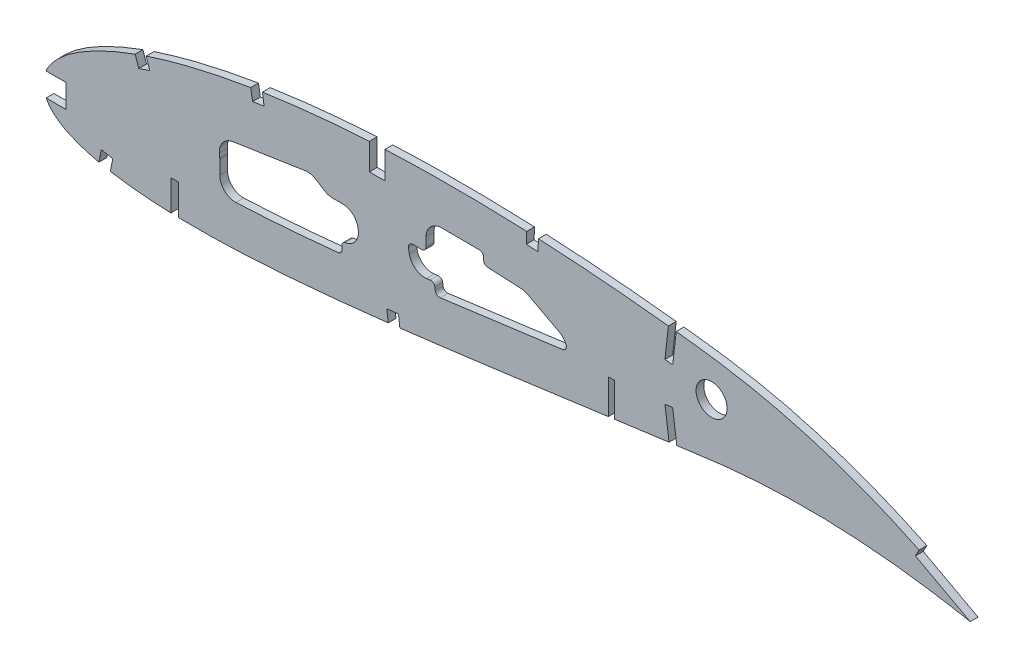
SolidWorks part; units mm, degrees
material "Plywood"
ref_plane "Front Plane" through (0, 0, 0) normal (0, 0, 1) x (1, 0, 0)
ref_plane "Top Plane" through (0, 0, 0) normal (0, 1, 0) x (1, 0, 0)
ref_plane "Right Plane" through (0, 0, 0) normal (1, 0, 0) x (0, 0, -1)
curve "Curve1"
  spline degree 3 poles (383.949, 0.5986, 0) (383.9196, 0.6168, 0) (383.802, 0.6894, 0) (383.5372, 0.8518, 0) (383.0962, 1.1224, 0) (382.4788, 1.4992, 0) (381.6856, 1.9812, 0) (380.716, 2.5651, 0) (379.5708, 3.249, 0) (378.2502, 4.0295, 0) (376.7543, 4.9032, 0) (375.0838, 5.8664, 0) (373.2387, 6.9137, 0) (371.2197, 8.0407, 0) (369.0276, 9.2423, 0) (366.6628, 10.5128, 0) (364.1261, 11.8459, 0) (361.4185, 13.2358, 0) (358.5405, 14.6749, 0) (355.4934, 16.1571, 0) (352.2782, 17.675, 0) (348.8962, 19.2207, 0) (345.3491, 20.7877, 0) (341.638, 22.3663, 0) (337.765, 23.9497, 0) (333.7318, 25.5289, 0) (329.5407, 27.0966, 0) (325.1933, 28.6428, 0) (320.6929, 30.1607, 0) (316.0417, 31.6403, 0) (311.2431, 33.0737, 0) (306.2997, 34.4516, 0) (301.2157, 35.767, 0) (295.9944, 37.0101, 0) (290.6401, 38.1728, 0) (285.1572, 39.2479, 0) (279.5502, 40.2249, 0) (273.8346, 41.1028, 0) (268.1025, 41.8331, 0) (262.3821, 42.5494, 0) (256.6703, 43.2222, 0) (250.8886, 43.8666, 0) (245.0428, 44.4788, 0) (239.1384, 45.057, 0) (233.1816, 45.5987, 0) (227.1785, 46.1022, 0) (221.135, 46.5647, 0) (215.0573, 46.9856, 0) (208.9515, 47.361, 0) (202.8242, 47.6908, 0) (196.6815, 47.9725, 0) (190.5298, 48.2044, 0) (184.3757, 48.385, 0) (178.2255, 48.5125, 0) (172.0859, 48.5861, 0) (165.9633, 48.6039, 0) (159.8643, 48.5655, 0) (153.7954, 48.4696, 0) (147.7632, 48.3149, 0) (141.7741, 48.1011, 0) (135.8345, 47.8283, 0) (129.951, 47.4942, 0) (124.1299, 47.1009, 0) (118.3778, 46.6469, 0) (112.701, 46.1319, 0) (107.1053, 45.5581, 0) (101.5971, 44.9239, 0) (96.1822, 44.2312, 0) (90.8666, 43.4813, 0) (85.6562, 42.6738, 0) (80.5566, 41.8111, 0) (75.5733, 40.894, 0) (70.7116, 39.9252, 0) (65.9768, 38.9049, 0) (61.3739, 37.8363, 0) (56.9076, 36.7211, 0) (52.5828, 35.5615, 0) (48.4038, 34.3602, 0) (44.375, 33.1199, 0) (40.5009, 31.842, 0) (36.7845, 30.5314, 0) (33.2304, 29.1889, 0) (29.8413, 27.8188, 0) (26.6212, 26.4228, 0) (23.5724, 25.0052, 0) (20.6984, 23.5677, 0) (18.0014, 22.1143, 0) (15.4839, 20.6472, 0) (13.1483, 19.1691, 0) (10.9958, 17.6837, 0) (9.0293, 16.1921, 0) (7.2493, 14.698, 0) (5.6571, 13.2036, 0) (4.255, 11.71, 0) (3.0428, 10.2198, 0) (2.0222, 8.7343, 0) (1.1933, 7.2547, 0) (0.558, 5.7822, 0) (0.1157, 4.3176, 0) (-0.1263, 2.863, 0) (-0.1866, 1.4174, 0) (-0.0621, 0.4718, 0) (0, 0, 0) knots 0 0 0 0 0.000254 0.001015 0.002283 0.004057 0.006331 0.009105 0.012374 0.016134 0.02038 0.025106 0.030306 0.035972 0.0421 0.048678 0.055702 0.06316 0.071046 0.07935 0.088063 0.097176 0.106678 0.116562 0.126814 0.137428 0.148394 0.1597 0.171338 0.183298 0.19557 0.208144 0.221012 0.234162 0.247587 0.261277 0.275223 0.289414 0.303771 0.317689 0.331784 0.34604 0.360444 0.374983 0.38964 0.404403 0.419257 0.434187 0.449177 0.464215 0.479284 0.49437 0.509458 0.524532 0.539579 0.554583 0.56953 0.584403 0.599191 0.613877 0.628447 0.642889 0.657186 0.671326 0.685294 0.699078 0.712665 0.726043 0.739198 0.752118 0.764792 0.777208 0.789356 0.801224 0.812804 0.824083 0.835055 0.84571 0.856038 0.866034 0.875689 0.884998 0.893953 0.902553 0.910789 0.918661 0.926166 0.933303 0.940071 0.946475 0.952518 0.958205 0.963547 0.968557 0.97325 0.977651 0.981787 0.985694 0.989415 0.993001 0.996508 1 1 1 1
curve "Curve2"
  spline degree 3 poles (0, 0, 0) (0.0986, -0.4654, 0) (0.2962, -1.3985, 0) (0.8332, -2.7416, 0) (1.5434, -4.0328, 0) (2.4415, -5.2686, 0) (3.5218, -6.4485, 0) (4.7818, -7.574, 0) (6.2202, -8.6443, 0) (7.8352, -9.659, 0) (9.6244, -10.6191, 0) (11.5859, -11.5241, 0) (13.7178, -12.3737, 0) (16.0178, -13.1667, 0) (18.4831, -13.9043, 0) (21.1113, -14.5848, 0) (23.8995, -15.2091, 0) (26.845, -15.7756, 0) (29.9446, -16.2848, 0) (33.195, -16.7366, 0) (36.593, -17.1311, 0) (40.1351, -17.4676, 0) (43.8179, -17.7467, 0) (47.6377, -17.9687, 0) (51.5909, -18.1343, 0) (55.6735, -18.2428, 0) (59.8817, -18.2959, 0) (64.2115, -18.2945, 0) (68.6589, -18.238, 0) (73.2199, -18.1297, 0) (77.8902, -17.9689, 0) (82.6657, -17.7575, 0) (87.5419, -17.4976, 0) (92.5144, -17.1902, 0) (97.5791, -16.8365, 0) (102.7313, -16.4394, 0) (107.9665, -16, 0) (113.2801, -15.5207, 0) (118.6674, -15.0039, 0) (124.1237, -14.4514, 0) (129.6442, -13.8657, 0) (135.2241, -13.2487, 0) (140.8584, -12.6036, 0) (146.5422, -11.9317, 0) (152.2705, -11.2369, 0) (158.0381, -10.5203, 0) (163.84, -9.7848, 0) (169.6711, -9.0339, 0) (175.5259, -8.2674, 0) (181.3995, -7.4908, 0) (187.2862, -6.7036, 0) (193.1809, -5.9096, 0) (199.0781, -5.1115, 0) (204.9721, -4.3094, 0) (210.8578, -3.5066, 0) (216.7295, -2.7054, 0) (222.5817, -1.9059, 0) (228.409, -1.112, 0) (234.2055, -0.3236, 0) (239.9659, 0.4577, 0) (245.6847, 1.2295, 0) (251.3565, 1.9909, 0) (256.9754, 2.7413, 0) (262.5357, 3.4812, 0) (267.9487, 4.188, 0) (273.2002, 4.8993, 0) (278.3079, 5.4825, 0) (283.3519, 5.9802, 0) (288.3377, 6.3883, 0) (293.259, 6.7125, 0) (298.1104, 6.9553, 0) (302.886, 7.1201, 0) (307.5799, 7.2116, 0) (312.186, 7.2323, 0) (316.6983, 7.1886, 0) (321.1107, 7.0842, 0) (325.4171, 6.9238, 0) (329.6115, 6.7126, 0) (333.688, 6.4566, 0) (337.6405, 6.1594, 0) (341.4634, 5.828, 0) (345.1508, 5.4673, 0) (348.6971, 5.0813, 0) (352.0971, 4.6782, 0) (355.3453, 4.2606, 0) (358.4369, 3.8354, 0) (361.3669, 3.4069, 0) (364.1307, 2.9806, 0) (366.7239, 2.5605, 0) (369.1422, 2.1521, 0) (371.3821, 1.7594, 0) (373.4394, 1.3862, 0) (375.3115, 1.0371, 0) (376.9946, 0.7139, 0) (378.4864, 0.4219, 0) (379.7842, 0.1625, 0) (380.886, -0.0608, 0) (381.79, -0.247, 0) (382.4947, -0.3932, 0) (382.9989, -0.4995, 0) (383.3019, -0.5627, 0) (383.4365, -0.5914, 0) (383.4701, -0.5986, 0) knots 0 0 0 0 0.003638 0.007293 0.011028 0.014901 0.018963 0.023258 0.027821 0.032679 0.037853 0.043362 0.049215 0.055422 0.061989 0.068918 0.076211 0.083868 0.091887 0.100266 0.109 0.118085 0.127515 0.137285 0.147388 0.157816 0.168563 0.179619 0.190977 0.202627 0.21456 0.226767 0.239236 0.251959 0.264924 0.27812 0.291536 0.30516 0.318981 0.332985 0.347163 0.361499 0.375981 0.390597 0.405333 0.420175 0.43511 0.450124 0.465203 0.480333 0.495501 0.51069 0.525887 0.541078 0.556247 0.571382 0.586466 0.601485 0.616424 0.631269 0.646007 0.660621 0.675098 0.689423 0.703582 0.716908 0.730009 0.742952 0.755726 0.76832 0.780724 0.792927 0.804916 0.816679 0.828204 0.839475 0.850481 0.861208 0.871639 0.881763 0.891564 0.901027 0.910139 0.918884 0.927249 0.935221 0.942785 0.949928 0.956638 0.962904 0.968712 0.974054 0.978918 0.983297 0.98718 0.990561 0.993433 0.995791 0.99763 0.998946 0.999737 1 1 1 1
sketch "Sketch1" plane through (0, 0, 0) normal (0, 0, 1) x (1, 0, 0)
  line L23 (383.4597, -0.5986) -> (387.1511, -1.386)
  line L24 (383.9386, 0.5986) -> (387.1511, -1.386)
  spline S4 degree 3 poles (0, 0) (0.0986, -0.4654) (0.2962, -1.3984) (0.8332, -2.7416) (1.5433, -4.0327) (2.4415, -5.2684) (3.5217, -6.4484) (4.7816, -7.5738) (6.22, -8.6441) (7.835, -9.6587) (9.6242, -10.6188) (11.5856, -11.5238) (13.7174, -12.3733) (16.0173, -13.1663) (18.4826, -13.9039) (21.1108, -14.5844) (23.8989, -15.2087) (26.8443, -15.7751) (29.9438, -16.2844) (33.1941, -16.7361) (36.592, -17.1306) (40.134, -17.4671) (43.8167, -17.7462) (47.6365, -17.9682) (51.5895, -18.1338) (55.672, -18.2423) (59.88, -18.2954) (64.2098, -18.294) (68.657, -18.2375) (73.2179, -18.1293) (77.8881, -17.9684) (82.6634, -17.757) (87.5395, -17.4972) (92.5119, -17.1897) (97.5764, -16.836) (102.7286, -16.439) (107.9636, -15.9995) (113.2771, -15.5202) (118.6642, -15.0035) (124.1204, -14.451) (129.6407, -13.8653) (135.2204, -13.2483) (140.8546, -12.6033) (146.5382, -11.9314) (152.2664, -11.2365) (158.0338, -10.52) (163.8356, -9.7845) (169.6665, -9.0336) (175.5212, -8.2672) (181.3946, -7.4906) (187.2811, -6.7034) (193.1757, -5.9095) (199.0727, -5.1113) (204.9666, -4.3092) (210.8521, -3.5065) (216.7237, -2.7054) (222.5757, -1.9059) (228.4028, -1.112) (234.1992, -0.3236) (239.9594, 0.4576) (245.6781, 1.2294) (251.3497, 1.9908) (256.9684, 2.7413) (262.5286, 3.4811) (267.9415, 4.1879) (273.1928, 4.8992) (278.3003, 5.4823) (283.3443, 5.98) (288.3299, 6.3881) (293.2511, 6.7123) (298.1023, 6.9552) (302.8778, 7.1199) (307.5715, 7.2114) (312.1776, 7.2321) (316.6897, 7.1884) (321.102, 7.084) (325.4083, 6.9236) (329.6026, 6.7124) (333.679, 6.4564) (337.6313, 6.1592) (341.4541, 5.8278) (345.1414, 5.4671) (348.6876, 5.0812) (352.0875, 4.6781) (355.3357, 4.2605) (358.4272, 3.8353) (361.3571, 3.4068) (364.1208, 2.9805) (366.7139, 2.5604) (369.1322, 2.1521) (371.372, 1.7594) (373.4293, 1.3862) (375.3013, 1.0371) (376.9844, 0.7139) (378.4761, 0.4219) (379.7739, 0.1625) (380.8757, -0.0608) (381.7796, -0.247) (382.4844, -0.3932) (382.9885, -0.4994) (383.2915, -0.5627) (383.4261, -0.5914) (383.4597, -0.5986) knots 0 0 0 0 0.003638 0.007293 0.011028 0.014901 0.018963 0.023258 0.027821 0.032679 0.037853 0.043362 0.049215 0.055422 0.061989 0.068918 0.076211 0.083868 0.091887 0.100266 0.109 0.118085 0.127515 0.137285 0.147388 0.157816 0.168563 0.179619 0.190977 0.202627 0.21456 0.226767 0.239236 0.251959 0.264924 0.27812 0.291536 0.30516 0.318981 0.332985 0.347163 0.361499 0.375981 0.390597 0.405333 0.420175 0.43511 0.450124 0.465203 0.480333 0.495501 0.51069 0.525887 0.541078 0.556247 0.571382 0.586466 0.601485 0.616424 0.631269 0.646007 0.660621 0.675098 0.689423 0.703582 0.716908 0.730009 0.742952 0.755726 0.76832 0.780724 0.792927 0.804916 0.816679 0.828204 0.839475 0.850481 0.861208 0.871639 0.881763 0.891564 0.901027 0.910139 0.918884 0.927249 0.935221 0.942785 0.949928 0.956638 0.962904 0.968712 0.974054 0.978918 0.983297 0.98718 0.990561 0.993433 0.995791 0.99763 0.998946 0.999737 1 1 1 1
  spline S5 degree 3 poles (383.9386, 0.5986) (383.9092, 0.6167) (383.7916, 0.6893) (383.5268, 0.8518) (383.0858, 1.1223) (382.4685, 1.4991) (381.6752, 1.9811) (380.7057, 2.565) (379.5606, 3.2489) (378.24, 4.0294) (376.7441, 4.9031) (375.0736, 5.8662) (373.2286, 6.9135) (371.2097, 8.0405) (369.0176, 9.242) (366.6529, 10.5125) (364.1162, 11.8456) (361.4087, 13.2354) (358.5307, 14.6745) (355.4837, 16.1566) (352.2687, 17.6745) (348.8867, 19.2201) (345.3398, 20.7871) (341.6288, 22.3657) (337.7559, 23.949) (333.7228, 25.5282) (329.5317, 27.0959) (325.1845, 28.642) (320.6843, 30.1598) (316.0332, 31.6395) (311.2346, 33.0728) (306.2914, 34.4507) (301.2076, 35.766) (295.9864, 37.0091) (290.6322, 38.1717) (285.1495, 39.2469) (279.5426, 40.2238) (273.8272, 41.1017) (268.0952, 41.832) (262.375, 42.5482) (256.6633, 43.2211) (250.8818, 43.8654) (245.0361, 44.4776) (239.1319, 45.0558) (233.1753, 45.5974) (227.1724, 46.1009) (221.129, 46.5635) (215.0515, 46.9843) (208.9459, 47.3597) (202.8187, 47.6895) (196.6762, 47.9712) (190.5246, 48.2031) (184.3707, 48.3836) (178.2206, 48.5111) (172.0812, 48.5848) (165.9588, 48.6026) (159.86, 48.5642) (153.7912, 48.4683) (147.7592, 48.3136) (141.7702, 48.0998) (135.8308, 47.827) (129.9475, 47.4929) (124.1266, 47.0997) (118.3746, 46.6456) (112.6979, 46.1306) (107.1024, 45.5568) (101.5944, 44.9227) (96.1796, 44.23) (90.8641, 43.4801) (85.6539, 42.6727) (80.5544, 41.81) (75.5713, 40.8929) (70.7097, 39.9241) (65.975, 38.9039) (61.3722, 37.8353) (56.906, 36.7201) (52.5814, 35.5606) (48.4025, 34.3593) (44.3738, 33.119) (40.4998, 31.8412) (36.7835, 30.5306) (33.2295, 29.1881) (29.8405, 27.818) (26.6204, 26.4221) (23.5718, 25.0045) (20.6979, 23.5671) (18.0009, 22.1137) (15.4834, 20.6466) (13.148, 19.1685) (10.9955, 17.6833) (9.029, 16.1917) (7.2491, 14.6976) (5.657, 13.2033) (4.2548, 11.7097) (3.0427, 10.2196) (2.0221, 8.734) (1.1932, 7.2545) (0.558, 5.782) (0.1157, 4.3174) (-0.1263, 2.8629) (-0.1866, 1.4173) (-0.0621, 0.4717) (0, 0) knots 0 0 0 0 0.000254 0.001015 0.002283 0.004057 0.006331 0.009105 0.012374 0.016134 0.02038 0.025106 0.030306 0.035972 0.0421 0.048678 0.055702 0.06316 0.071046 0.07935 0.088063 0.097176 0.106678 0.116562 0.126814 0.137428 0.148394 0.1597 0.171338 0.183298 0.19557 0.208144 0.221012 0.234162 0.247587 0.261277 0.275223 0.289414 0.303771 0.317689 0.331784 0.34604 0.360444 0.374983 0.38964 0.404403 0.419257 0.434187 0.449177 0.464215 0.479284 0.49437 0.509458 0.524532 0.539579 0.554583 0.56953 0.584403 0.599191 0.613877 0.628447 0.642889 0.657186 0.671326 0.685294 0.699078 0.712665 0.726043 0.739198 0.752118 0.764792 0.777208 0.789356 0.801224 0.812804 0.824083 0.835055 0.84571 0.856038 0.866034 0.875689 0.884998 0.893953 0.902553 0.910789 0.918661 0.926166 0.933303 0.940071 0.946475 0.952518 0.958205 0.963547 0.968557 0.97325 0.977651 0.981787 0.985694 0.989415 0.993001 0.996508 1 1 1 1
extrude "Boss-Extrude1" add sketch "Sketch1" along normal blind 3.175
sketch "Sketch2" plane through (0, 0, 0) normal (0, 0, -1) x (-1, 0, 0)
  line L0 (-232.8305, 13.2238) -> (-230.2905, 13.2238)
  line L1 (-232.8305, -0.5032) -> (-232.8305, -2.8497)
  line L2 (-232.8305, 13.2238) -> (-232.8305, -0.5032)
  line L4 (-232.8305, -2.8497) -> (-230.2905, -1.6764)
  line L5 (-230.2905, -1.6764) -> (-230.2905, -0.5032)
  line L7 (-139.168, 47.9082) -> (-139.168, 36.8678)
  line L8 (-139.168, 36.8678) -> (-132.818, 36.8678)
  line L9 (-139.168, 47.9082) -> (-139.168, 49.4489)
  line L10 (-55.0305, -5.6829) -> (-55.0305, -17.799)
  line L12 (-139.168, 49.4489) -> (-132.818, 49.1679)
  line L13 (-132.818, 49.1679) -> (-132.818, 47.9082)
  line L14 (-51.8555, -5.6829) -> (-51.8555, -17.799)
  line L16 (-55.0305, -5.6829) -> (-51.8555, -5.6829)
  line L17 (-55.0305, -17.799) -> (-55.0305, -19.968)
  line L19 (-132.818, 47.9082) -> (-132.818, 36.8678)
  line L20 (-55.0305, -19.968) -> (-51.8555, -18.5014)
  line L21 (-51.8555, -18.5014) -> (-51.8555, -17.799)
  line L22 (-230.2905, 13.2238) -> (-230.2905, -0.5032)
extrude "Cut-Extrude1" cut sketch "Sketch2" against normal blind 7.62
sketch "Sketch3" plane through (0, 0, 0) normal (0, 0, -1) x (-1, 0, 0)
  circle A1 centre (-272.4199, 26.2554) radius 6.35
extrude "Cut-Extrude2" cut sketch "Sketch3" against normal blind 7.62
sketch "Sketch4" plane through (0, 0, 3.175) normal (0, 0, 1) x (1, 0, 0)
  line L0 (253.3978, 15.0563) -> (255.0785, 2.468)
  line L1 (253.3978, 15.0563) -> (255.0785, 2.468)
  line L2 (256.5449, 15.4765) -> (253.3978, 15.0563)
  line L3 (256.5449, 15.4765) -> (253.3978, 15.0563)
  line L4 (254.8081, 43.5209) -> (253.3898, 30.9004)
  line L5 (254.8081, 43.5209) -> (253.3898, 30.9004)
  line L6 (197.0245, 48.0319) -> (196.82, 43.2872)
  line L7 (197.0245, 48.0319) -> (196.82, 43.2872)
  line L8 (84.4023, 42.5499) -> (85.1717, 37.8779)
  line L9 (84.4023, 42.5499) -> (85.1717, 37.8779)
  line L10 (139.9591, -7.9331) -> (140.5078, -12.6647)
  line L11 (139.9591, -7.9331) -> (140.5078, -12.6647)
  line L12 (144.6885, -7.3719) -> (139.9591, -7.9331)
  line L13 (144.6885, -7.3719) -> (139.9591, -7.9331)
  line L14 (37.2314, 30.8049) -> (38.732, 26.3414)
  line L15 (37.2314, 30.8049) -> (38.732, 26.3414)
  line L16 (23.4683, -9.9368) -> (22.5446, -14.6116)
  line L17 (23.4683, -9.9368) -> (22.5446, -14.6116)
  line L18 (28.1358, -10.8598) -> (23.4683, -9.9368)
  line L19 (28.1358, -10.8598) -> (23.4683, -9.9368)
  line L20 (-0.4208, 6.5685) -> (9.1042, 6.5685)
  line L21 (-0.4208, 6.5685) -> (9.1042, 6.5685)
  line L22 (9.1042, -2.9565) -> (9.1042, 6.5685)
  line L23 (9.1042, -2.9565) -> (9.1042, 6.5685)
  line L24 (-0.4208, -2.9565) -> (9.1042, -2.9565)
  line L25 (-0.4208, -2.9565) -> (9.1042, -2.9565)
  line L26 (27.1866, -15.6474) -> (28.1358, -10.8598)
  line L27 (27.1866, -15.6474) -> (28.1358, -10.8598)
  line L28 (43.2462, 27.8589) -> (41.731, 32.3666)
  line L29 (43.2462, 27.8589) -> (41.731, 32.3666)
  line L30 (38.732, 26.3414) -> (43.2462, 27.8589)
  line L31 (38.732, 26.3414) -> (43.2462, 27.8589)
  line L32 (89.8796, 38.5972) -> (89.1598, 43.3084)
  line L33 (89.8796, 38.5972) -> (89.1598, 43.3084)
  line L34 (85.1717, 37.8779) -> (89.8796, 38.5972)
  line L35 (85.1717, 37.8779) -> (89.8796, 38.5972)
  line L36 (145.2504, -12.1074) -> (144.6885, -7.3719)
  line L37 (145.2504, -12.1074) -> (144.6885, -7.3719)
  line L38 (201.5767, 43.0552) -> (201.8123, 47.81)
  line L39 (201.5767, 43.0552) -> (201.8123, 47.81)
  line L40 (196.82, 43.2872) -> (201.5767, 43.0552)
  line L41 (196.82, 43.2872) -> (201.5767, 43.0552)
  line L42 (258.2214, 2.8872) -> (256.5449, 15.4765)
  line L43 (258.2214, 2.8872) -> (256.5449, 15.4765)
  line L44 (256.5449, 30.5458) -> (258.0069, 43.1557)
  line L45 (256.5449, 30.5458) -> (258.0069, 43.1557)
  line L46 (253.3898, 30.9004) -> (256.5449, 30.5458)
  line L47 (253.3898, 30.9004) -> (256.5449, 30.5458)
  line L48 (-0.4208, -2.9565) -> (-0.4208, 6.5685)
  line L49 (22.5446, -14.6116) -> (21.6044, -19.3694)
  line L50 (21.6044, -19.3694) -> (26.2707, -20.2914)
  line L51 (26.2707, -20.2914) -> (27.1866, -15.6474)
  line L52 (84.4023, 42.5499) -> (89.1598, 43.3084)
  line L53 (140.5078, -12.6647) -> (145.2504, -12.1074)
  line L54 (197.0245, 48.0319) -> (201.8123, 47.81)
  line L55 (254.8081, 43.5209) -> (258.0069, 43.1557)
  line L56 (255.0785, 2.468) -> (255.3213, 0.6492)
  line L57 (255.3213, 0.6492) -> (258.4684, 1.0693)
  line L58 (258.4684, 1.0693) -> (258.2214, 2.8872)
  spline S0 degree 3 poles (-926.9744, 1759.2326) (537.7565, -123.458) (52.1572, 240.1265) (-170.353, -168.2622) (607.2071, -1871.7177) knots -132.16721 -132.16721 -132.16721 -132.16721 0.273428 83.465389 83.465389 83.465389 83.465389 only from (41.731, 32.3666) to (37.2314, 30.8049)
  spline S1 degree 3 poles (41.731, 32.3666) (41.3193, 32.2289) (39.8151, 31.7207) (38.3166, 31.1959) (37.2314, 30.8049) knots 0 0 0 0 0.273428 1 1 1 1
extrude "Cut-Extrude3" cut sketch "Sketch4" against normal through all
sketch "Sketch5" plane through (0, 0, 3.175) normal (0, 0, 1) x (1, 0, 0)
  line L0 (127.2472, 20.1038) -> (116.054, 20.1038)
  line L3 (108.9829, 24.5572) -> (71.3232, 18.8038)
  line L9 (71.7945, 11.0811) -> (71.7945, -1.3909)
  line L10 (121.9103, 2.1782) -> (121.3808, 6.7439)
  line L11 (121.3808, 6.7439) -> (129.4239, 7.6984)
  line L12 (127.2472, 20.1038) -> (129.4239, 7.6984)
  line L13 (125.7357, 28.718) -> (131.3266, -3.1455) construction
  line L14 (79.1937, 35.0998) -> (49.8476, 28.1498) construction
  line L15 (121.3808, 6.7439) -> (149.0188, 10.0236) construction
  line L16 (145.518, 20.1038) -> (116.054, 20.1038) construction
  line L17 (70.732, 22.3937) -> (63.3562, 20.647) construction
  line L18 (71.3232, 18.8038) -> (71.7945, 11.0811)
  line L19 (116.054, 20.1038) -> (108.9829, 24.5572)
  line L20 (126.468, 40.8897) -> (96.4185, 37.8427) construction
  line L21 (116.054, 29.3663) -> (108.3673, 28.5869) construction
  line L22 (150.1388, 10.1565) -> (159.3602, 11.2507)
  line L23 (159.3602, 11.2507) -> (159.9102, 6.616)
  line L24 (213.5265, 13.7782) -> (213.5265, 17.324)
  line L25 (213.5265, 17.324) -> (213.5265, 17.324)
  line L26 (213.5265, 17.324) -> (196.0856, 26.5391)
  line L27 (196.0856, 26.5391) -> (179.3537, 27.3552)
  line L28 (179.3537, 27.3552) -> (179.5415, 31.7126)
  line L29 (155.932, 31.7324) -> (155.932, 20.1038)
  line L30 (131.6947, 7.9678) -> (159.3602, 11.2507) construction
  line L31 (148.3934, 20.1038) -> (150.1388, 10.1565)
  line L32 (146.2503, 32.3176) -> (151.8412, 0.454) construction
  line L33 (155.932, 20.1038) -> (148.3934, 20.1038)
  line L36 (43.0125, 21.0812) -> (53.443, 0.6671) construction
  line L37 (135.993, 30.5178) -> (141.5839, -1.3457) construction
  line L38 (231.5605, 19.5738) -> (198.9045, 36.828) construction
  line L110 (53.443, 0.6671) -> (61.3805, 0.6671) construction
  line L111 (61.3805, 0.6671) -> (61.3805, -11.942) construction
  line L112 (133.4644, -7.0518) -> (132.9219, -2.3736) construction
  line L113 (132.9219, -2.3736) -> (150.2459, -0.3179) construction
  line L114 (150.2459, -0.3179) -> (150.8034, -5.0156) construction
  line L115 (223.9405, 4.6886) -> (223.9405, 19.5738) construction
  line L116 (223.9405, 19.5738) -> (231.5605, 19.5738) construction
  line L125 (198.9045, 36.828) -> (190.204, 37.2524) construction
  line L126 (190.204, 37.2524) -> (190.4019, 41.8451) construction
  line L127 (145.518, 41.8768) -> (145.518, 30.5178) construction
  line L128 (145.518, 30.5178) -> (126.468, 30.5178) construction
  line L129 (126.468, 30.5178) -> (126.468, 40.8897) construction
  line L130 (96.4185, 37.8427) -> (97.1157, 33.279) construction
  line L131 (97.1157, 33.279) -> (79.9261, 30.6529) construction
  line L132 (79.9261, 30.6529) -> (79.1937, 35.0998) construction
  line L133 (49.8476, 28.1498) -> (51.2885, 23.8632) construction
  line L134 (51.2885, 23.8632) -> (43.0125, 21.0812) construction
  line L135 (59.8167, 11.0811) -> (71.7945, 11.0811) construction
  line L136 (57.7836, 15.06) -> (59.8167, 11.0811) construction
  line L137 (64.4778, 17.3103) -> (57.7836, 15.06) construction
  line L138 (63.3562, 20.647) -> (64.4778, 17.3103) construction
  line L139 (71.3232, 18.8038) -> (70.732, 22.3937) construction
  line L140 (116.054, 20.1038) -> (116.054, 29.3663) construction
  line L141 (108.3673, 28.5869) -> (108.9829, 24.5572) construction
  line L142 (155.932, 20.1038) -> (126.468, 20.1038) construction
  spline S0 degree 1 poles (159.9102, 6.616) (213.5265, 13.7782) knots 0 0 1 1 construction
  spline S1 degree 1 poles (179.5415, 31.7126) (155.932, 31.7324) knots 0 0 1 1 construction
  spline S2 degree 1 poles (71.7945, -1.3909) (121.9103, 2.1782) knots 0 0 1 1 construction
  spline S3 degree 3 poles (159.9102, 6.616) (164.3746, 7.1833) (173.2961, 8.3408) (186.698, 10.1292) (200.1064, 11.946) (209.054, 13.1676) (213.5265, 13.7782) knots 0.142323 0.142323 0.142323 0.142323 0.325945 0.509567 0.693189 0.876811 0.876811 0.876811 0.876811
  spline S4 degree 3 poles (179.5415, 31.7126) (177.5729, 31.7494) (173.6348, 31.8061) (167.7311, 31.8388) (161.8287, 31.8179) (157.8978, 31.7672) (155.932, 31.7324) knots 0.237664 0.237664 0.237664 0.237664 0.371263 0.504863 0.638463 0.772063 0.772063 0.772063 0.772063
  spline S5 degree 3 poles (71.7945, -1.3909) (75.9548, -1.2787) (84.2564, -0.9305) (96.788, -0.1167) (109.3347, 0.9275) (117.723, 1.7458) (121.9103, 2.1782) knots 0.147972 0.147972 0.147972 0.147972 0.32451 0.501048 0.677586 0.854123 0.854123 0.854123 0.854123
  spline S36 degree 3 poles (61.3805, -11.942) (67.4058, -11.9519) (73.4269, -11.8005) (85.4632, -11.2817) (91.4772, -10.9139) (103.4919, -10.0249) (109.4942, -9.5033) (121.4867, -8.3518) (127.4774, -7.7211) (133.4644, -7.0518) knots 0 0 0 0 0.25 0.25 0.5 0.5 0.75 0.75 1 1 1 1 construction
  spline S37 degree 3 poles (150.8034, -5.0156) (163.0088, -3.5214) (175.2005, -1.9186) (199.5744, 1.3563) (211.7567, 3.028) (223.9405, 4.6886) knots 0 0 0 0 0.5 0.5 1 1 1 1 construction
  spline S41 degree 3 poles (190.4019, 41.8451) (182.9238, 42.0966) (175.442, 42.2337) (160.4781, 42.2535) (152.996, 42.1371) (145.518, 41.8768) knots 0 0 0 0 0.5 0.5 1 1 1 1 construction
  spline S42 degree 3 poles (126.468, 40.8897) (116.4216, 40.191) (106.3976, 39.1999) (96.4185, 37.8427) knots 0 0 0 0 1 1 1 1 construction
  spline S43 degree 3 poles (79.1937, 35.0998) (74.2467, 34.1892) (69.3194, 33.1701) (59.5289, 30.8714) (54.667, 29.5931) (49.8476, 28.1498) knots 0 0 0 0 0.5 0.5 1 1 1 1 construction
  dimension "D1" = 10.414
  dimension "D2" = 10.414
  dimension "D3" = 10.414
extrude "Cut-Extrude4" cut sketch "Sketch5" against normal blind 7.62
fillet "Fillet1" radius 6.35 11 edges at (150.1388, 10.1565, 1.5875) (213.5265, 17.324, 1.5875) (155.932, 31.7324, 1.5875) (196.0856, 26.5391, 1.5875) (129.4239, 7.6984, 1.5875) (127.2472, 20.1038, 1.5875) (116.054, 20.1038, 1.5875) (108.9829, 24.5572, 1.5875) (71.7945, -1.3909, 1.5875) (71.7945, 11.0811, 1.5875) (71.3232, 18.8038, 1.5875)
fillet "Fillet2" radius 1.778 9 edges at (213.5265, 13.7782, 1.5875) (179.3537, 27.3552, 1.5875) (179.5415, 31.7126, 1.5875) (159.9102, 6.616, 1.5875) (159.3602, 11.2507, 1.5875) (155.932, 20.1038, 1.5875) (148.3934, 20.1038, 1.5875) (121.9103, 2.1782, 1.5875) (121.3808, 6.7439, 1.5875)
sketch "Sketch6" plane through (0, 0, 3.175) normal (0, 0, 1) x (1, 0, 0)
  line L0 (357.0755, 15.3806) -> (355.5684, 12.586)
  line L1 (357.0755, 15.3806) -> (379.4317, 3.3241)
  line L2 (355.5684, 12.586) -> (377.9247, 0.5296)
  line L3 (379.4317, 3.3241) -> (377.9247, 0.5296)
  line L4 (383.4597, -0.5986) -> (387.1511, -1.386) construction
  line L5 (387.1511, -1.386) -> (383.9386, 0.5986) construction
  line L6 (383.4597, -0.5986) -> (387.1511, -1.386)
  line L7 (387.1511, -1.386) -> (383.9386, 0.5986)
  spline S0 degree 3 poles (-542.4415, 1804.8935) (-113.3574, -70.3051) (74.8659, -21.0222) (267.9415, 4.1879) (273.1928, 4.8992) (278.3003, 5.4823) (283.3443, 5.98) (288.3299, 6.3881) (293.2511, 6.7123) (298.1023, 6.9552) (302.8778, 7.1199) (307.5715, 7.2114) (312.1776, 7.2321) (316.6897, 7.1884) (321.102, 7.084) (325.4083, 6.9236) (329.6026, 6.7124) (333.679, 6.4564) (337.6313, 6.1592) (341.4541, 5.8278) (345.1414, 5.4671) (348.6876, 5.0812) (352.0875, 4.6781) (355.3357, 4.2605) (358.4272, 3.8353) (361.3571, 3.4068) (364.1208, 2.9805) (366.7139, 2.5604) (369.1322, 2.1521) (371.372, 1.7594) (373.4293, 1.3862) (375.3013, 1.0371) (376.9844, 0.7139) (378.4761, 0.4219) (379.7739, 0.1625) (380.8757, -0.0608) (381.7796, -0.247) (382.4844, -0.3932) (382.9885, -0.4994) (395.9313, -3.2009) (407.5807, -11.1879) (834.9552, 1947.0393) knots -0.774428 -0.774428 -0.774428 -0.774428 0.689423 0.703582 0.716908 0.730009 0.742952 0.755726 0.76832 0.780724 0.792927 0.804916 0.816679 0.828204 0.839475 0.850481 0.861208 0.871639 0.881763 0.891564 0.901027 0.910139 0.918884 0.927249 0.935221 0.942785 0.949928 0.956638 0.962904 0.968712 0.974054 0.978918 0.983297 0.98718 0.990561 0.993433 0.995791 0.99763 0.998946 0.999737 1.098895 1.098895 1.098895 1.098895 only from (258.2187, 2.9074) to (383.4597, -0.5986) construction
  spline S1 degree 3 poles (1469.2081, 1679.6305) (405.9756, -18.6386) (396.1036, -6.8626) (383.5268, 0.8518) (383.0858, 1.1223) (382.4685, 1.4991) (381.6752, 1.9811) (380.7057, 2.565) (379.5606, 3.2489) (378.24, 4.0294) (376.7441, 4.9031) (375.0736, 5.8662) (373.2286, 6.9135) (371.2097, 8.0405) (369.0176, 9.242) (366.6529, 10.5125) (364.1162, 11.8456) (361.4087, 13.2354) (358.5307, 14.6745) (355.4837, 16.1566) (352.2687, 17.6745) (348.8867, 19.2201) (345.3398, 20.7871) (341.6288, 22.3657) (337.7559, 23.949) (333.7228, 25.5282) (329.5317, 27.0959) (325.1845, 28.642) (320.6843, 30.1598) (316.0332, 31.6395) (311.2346, 33.0728) (306.2914, 34.4507) (301.2076, 35.766) (295.9864, 37.0091) (290.6322, 38.1717) (285.1495, 39.2469) (279.5426, 40.2238) (273.8272, 41.1017) (268.0952, 41.832) (22.2183, 72.6192) (-236.0113, -11.7677) (-104.1696, 1960.0263) knots -0.106155 -0.106155 -0.106155 -0.106155 0.000254 0.001015 0.002283 0.004057 0.006331 0.009105 0.012374 0.016134 0.02038 0.025106 0.030306 0.035972 0.0421 0.048678 0.055702 0.06316 0.071046 0.07935 0.088063 0.097176 0.106678 0.116562 0.126814 0.137428 0.148394 0.1597 0.171338 0.183298 0.19557 0.208144 0.221012 0.234162 0.247587 0.261277 0.275223 0.289414 0.303771 0.317689 2.110646 2.110646 2.110646 2.110646 only from (383.9386, 0.5986) to (257.9959, 43.0613) construction
  spline S2 degree 3 poles (258.2187, 2.9074) (259.6625, 3.0996) (262.9389, 3.5347) (267.9415, 4.1879) (273.1928, 4.8992) (278.3003, 5.4823) (283.3443, 5.98) (288.3299, 6.3881) (293.2511, 6.7123) (298.1023, 6.9552) (302.8778, 7.1199) (307.5715, 7.2114) (312.1776, 7.2321) (316.6897, 7.1884) (321.102, 7.084) (325.4083, 6.9236) (329.6026, 6.7124) (333.679, 6.4564) (337.6313, 6.1592) (341.4541, 5.8278) (345.1414, 5.4671) (348.6876, 5.0812) (352.0875, 4.6781) (355.3357, 4.2605) (358.4272, 3.8353) (361.3571, 3.4068) (364.1208, 2.9805) (366.7139, 2.5604) (369.1322, 2.1521) (371.372, 1.7594) (373.4293, 1.3862) (375.3013, 1.0371) (376.9844, 0.7139) (378.4761, 0.4219) (379.7739, 0.1625) (380.8757, -0.0608) (381.7796, -0.247) (382.4844, -0.3932) (382.9885, -0.4994) (383.2915, -0.5627) (383.4261, -0.5914) (383.4597, -0.5986) knots 0.678267 0.678267 0.678267 0.678267 0.689423 0.703582 0.716908 0.730009 0.742952 0.755726 0.76832 0.780724 0.792927 0.804916 0.816679 0.828204 0.839475 0.850481 0.861208 0.871639 0.881763 0.891564 0.901027 0.910139 0.918884 0.927249 0.935221 0.942785 0.949928 0.956638 0.962904 0.968712 0.974054 0.978918 0.983297 0.98718 0.990561 0.993433 0.995791 0.99763 0.998946 0.999737 1 1 1 1
  spline S3 degree 3 poles (383.9386, 0.5986) (383.9092, 0.6167) (383.7916, 0.6893) (383.5268, 0.8518) (383.0858, 1.1223) (382.4685, 1.4991) (381.6752, 1.9811) (380.7057, 2.565) (379.5606, 3.2489) (378.24, 4.0294) (376.7441, 4.9031) (375.0736, 5.8662) (373.2286, 6.9135) (371.2097, 8.0405) (369.0176, 9.242) (366.6529, 10.5125) (364.1162, 11.8456) (361.4087, 13.2354) (358.5307, 14.6745) (355.4837, 16.1566) (352.2687, 17.6745) (348.8867, 19.2201) (345.3398, 20.7871) (341.6288, 22.3657) (337.7559, 23.949) (333.7228, 25.5282) (329.5317, 27.0959) (325.1845, 28.642) (320.6843, 30.1598) (316.0332, 31.6395) (311.2346, 33.0728) (306.2914, 34.4507) (301.2076, 35.766) (295.9864, 37.0091) (290.6322, 38.1717) (285.1495, 39.2469) (279.5426, 40.2238) (273.8272, 41.1017) (268.0952, 41.832) (262.8117, 42.4936) (259.4638, 42.8908) (257.9959, 43.0613) knots 0 0 0 0 0.000254 0.001015 0.002283 0.004057 0.006331 0.009105 0.012374 0.016134 0.02038 0.025106 0.030306 0.035972 0.0421 0.048678 0.055702 0.06316 0.071046 0.07935 0.088063 0.097176 0.106678 0.116562 0.126814 0.137428 0.148394 0.1597 0.171338 0.183298 0.19557 0.208144 0.221012 0.234162 0.247587 0.261277 0.275223 0.289414 0.303771 0.317689 0.32855 0.32855 0.32855 0.32855
  dimension "D1" = 3.175
  dimension "D2" = 25.4
extrude "Cut-Extrude5" cut sketch "Sketch6" against normal through all contours L3 L1 L0 L2 | L1 S3 | L7 S3 L3 S2 L6 region at (367.5001, 7.9551, 3.175) region at (368.2813, 9.4569, 3.175) region at (381.5092, 0.837, 3.175)
move or copy body "Body-Move/Copy1" [suppressed] bodies to move or copy 120 121 parameters "D1"=0, "D2"=0, "D3"=0
